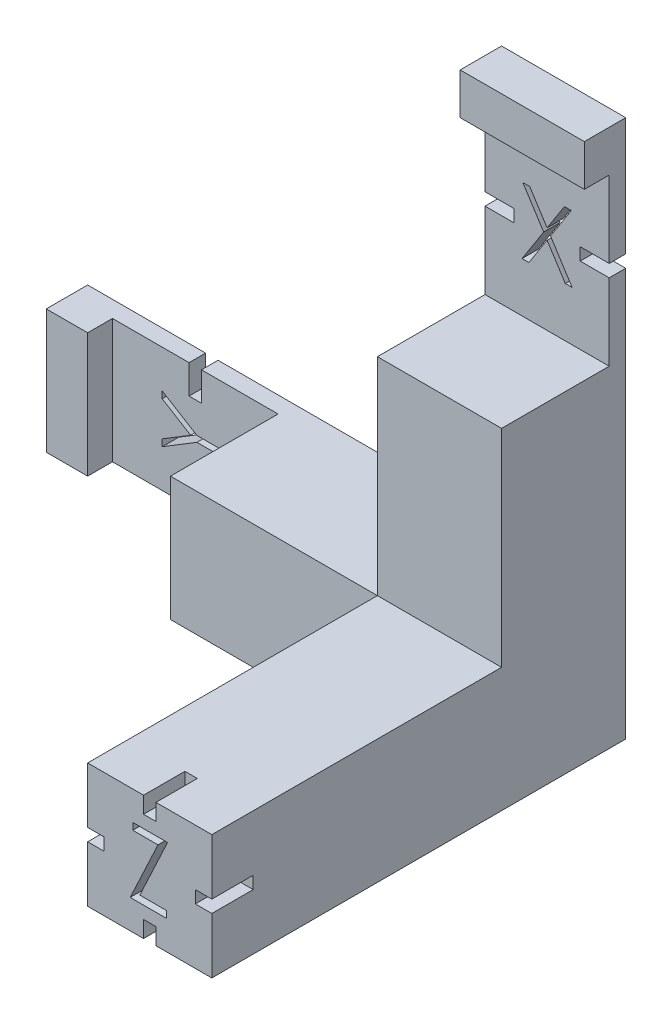
SolidWorks part; units mm, degrees
ref_plane "Alzado" through (0, 0, 0) normal (0, 0, 1) x (1, 0, 0)
ref_plane "Planta" through (0, 0, 0) normal (0, 1, 0) x (1, 0, 0)
ref_plane "Vista lateral" through (0, 0, 0) normal (1, 0, 0) x (0, 0, -1)
sketch "Croquis2" plane through (0, 0, 0) normal (0, 0, 1) x (1, 0, 0)
  line L1 (0, 0) -> (-15, 0)
  line L2 (0, 0) -> (0, 40)
  line L3 (0, 40) -> (-15, 40)
  line L4 (-15, 0) -> (-15, 40)
  line L5 (0, 0) -> (-40, 0)
  line L6 (0, 0) -> (0, 15)
  line L7 (0, 15) -> (-40, 15)
  line L8 (-40, 0) -> (-40, 15)
  dimension "D1" = 40
  dimension "D2" = 40
  dimension "D3" = 15
  dimension "D4" = 15
extrude "Saliente-Extruir1" add sketch "Croquis2" along normal blind 15 contours L8 L5 L4 L7 | L7 L2 L3 L4 region at (-27.5, 7.5, 0) region at (-7.5, 27.5, 0)
extrude "Saliente-Extruir2" add sketch "Croquis2<3>" along normal blind 50 contours L2 L7 L4 L1 region at (-7.5, 7.5, 0)
sketch "Croquis2<3>" plane through (0, 0, 0) normal (0, 0, 1) x (1, 0, 0) same geometry as "Croquis2"
sketch "Croquis3" plane through (0, 0, 0) normal (0, 0, 1) x (1, 0, 0)
  line L1 (-15, 40) -> (0, 40)
  line L2 (-15, 40) -> (-15, 60)
  line L3 (-15, 60) -> (0, 60)
  line L4 (0, 40) -> (0, 60)
  line L5 (-40, 15) -> (-60, 15)
  line L6 (-40, 15) -> (-40, 0)
  line L7 (-40, 0) -> (-60, 0)
  line L8 (-60, 15) -> (-60, 0)
  line L9 (-15, 60) -> (0, 60)
  line L10 (-15, 60) -> (-15, 65)
  line L11 (-15, 65) -> (0, 65)
  line L12 (0, 60) -> (0, 65)
  line L13 (-60, 15) -> (-65, 15)
  line L14 (-60, 15) -> (-60, 0)
  line L15 (-60, 0) -> (-65, 0)
  line L16 (-65, 15) -> (-65, 0)
  dimension "D1" = 20
  dimension "D2" = 20
  dimension "D3" = 5
  dimension "D4" = 5
extrude "Saliente-Extruir3" add sketch "Croquis3" along normal blind 2 contours L5 L8 L7 L6 | L1 L4 L3 L2 region at (-7.5, 50, 0) region at (-50, 7.5, 0)
extrude "Saliente-Extruir4" add sketch "Croquis3<3>" along normal blind 5 contours L13 L16 L15 L8 | L3 L12 L11 L10 region at (-7.5, 62.5, 0) region at (-62.5, 7.5, 0)
sketch "Croquis3<3>" plane through (0, 0, 0) normal (0, 0, 1) x (1, 0, 0) same geometry as "Croquis3"
sketch "Croquis4" plane through (0, 0, 2) normal (0, 0, 1) x (1, 0, 0)
  line L0 (-15, 46) -> (0, 46) construction
  line L1 (-15, 40) -> (-15, 60) construction
  line L2 (0, 40) -> (0, 60) construction
  line L3 (0, 40) -> (-15, 40) construction
  line L4 (-46, 15) -> (-46, 0) construction
  line L5 (-40, 15) -> (-60, 15) construction
  line L6 (-40, 0) -> (-60, 0) construction
  line L7 (-40, 0) -> (-40, 15) construction
  line L8 (-15, 50) -> (-11.5, 50) construction
  line L10 (0, 50) -> (-3.5, 50) construction
  line L11 (-50, 15) -> (-50, 11.5) construction
  line L12 (-50, 0) -> (-50, 3.5) construction
  line L13 (-7.5, 60) -> (-7.5, 40) construction
  line L14 (-15, 50.75) -> (-11.5, 50.75)
  line L15 (-15, 50.75) -> (-15, 49.25)
  line L16 (-15, 49.25) -> (-11.5, 49.25)
  line L17 (-11.5, 50.75) -> (-11.5, 49.25)
  line L18 (-15, 60) -> (0, 60) construction
  line L19 (0, 49.25) -> (-3.5, 49.25)
  line L20 (-3.5, 50.75) -> (-3.5, 49.25)
  line L21 (0, 50.75) -> (-3.5, 50.75)
  line L22 (0, 50.75) -> (0, 49.25)
  line L23 (-60, 7.5) -> (-46, 7.5) construction
  line L24 (-50.75, 15) -> (-49.25, 15)
  line L25 (-50.75, 15) -> (-50.75, 11.5)
  line L26 (-50.75, 11.5) -> (-49.25, 11.5)
  line L27 (-49.25, 15) -> (-49.25, 11.5)
  line L28 (-60, 15) -> (-60, 0) construction
  line L29 (-50.75, 3.5) -> (-49.25, 3.5)
  line L30 (-49.25, 0) -> (-49.25, 3.5)
  line L31 (-50.75, 0) -> (-49.25, 0)
  line L32 (-50.75, 0) -> (-50.75, 3.5)
  text T0 "X" font "Century Gothic" height 8
  text T1 "Y" font "Century Gothic" height 8
  point P30 (-11.5, 50)
  dimension "D1" = 6
  dimension "D2" = 6
  dimension "D3" = 3.5
  dimension "D4" = 3.5
  dimension "D5" = 3.5
  dimension "D6" = 3.5
  dimension "D7" = 1.5
  dimension "D8" = 1.5
extrude "Cortar-Extruir1" cut sketch "Croquis4" against normal blind 15
sketch "Croquis5" plane through (0, 0, 50) normal (0, 0, 1) x (1, 0, 0)
  line L0 (-15, 3.5) -> (0, 3.5) construction
  line L1 (0, 0) -> (-15, 0) construction
  line L2 (-7.5, 15) -> (-7.5, 0) construction
  line L3 (0, 15) -> (-15, 15) construction
  line L4 (-15, 7.5) -> (0, 7.5) construction
  line L5 (-15, 0) -> (-15, 15) construction
  line L6 (0, 0) -> (0, 15) construction
  line L7 (0, 15) -> (-15, 15) construction
  line L8 (-8.25, 15) -> (-6.75, 15)
  line L9 (-8.25, 15) -> (-8.25, 13)
  line L10 (-8.25, 13) -> (-6.75, 13)
  line L11 (-6.75, 15) -> (-6.75, 13)
  line L12 (-15, 0) -> (-15, 15) construction
  line L13 (-8.25, 2) -> (-6.75, 2)
  line L14 (-6.75, 0) -> (-6.75, 2)
  line L15 (-8.25, 0) -> (-6.75, 0)
  line L16 (-8.25, 0) -> (-8.25, 2)
  line L17 (-15, 15) -> (0, 0) construction
  line L18 (0, 8.25) -> (-2, 8.25)
  line L19 (0, 8.25) -> (0, 6.75)
  line L20 (0, 6.75) -> (-2, 6.75)
  line L21 (-2, 8.25) -> (-2, 6.75)
  line L22 (-13, 8.25) -> (-13, 6.75)
  line L23 (-15, 6.75) -> (-13, 6.75)
  line L24 (-15, 8.25) -> (-15, 6.75)
  line L25 (-15, 8.25) -> (-13, 8.25)
  text T0 "Z" font "Century Gothic" height 8
  point P2 (-7.5, 13)
  dimension "D1" = 3.5
  dimension "D2" = 1.5
  dimension "D3" = 2
extrude "Cortar-Extruir2" cut sketch "Croquis5" against normal blind 5
